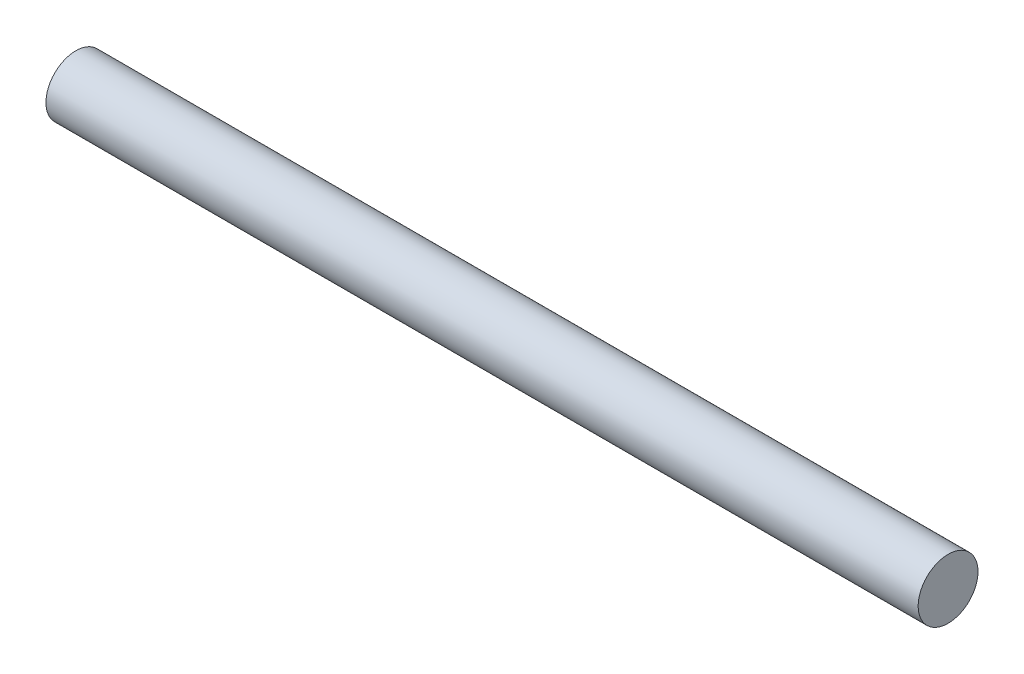
SolidWorks part; units mm, degrees
ref_plane "Front Plane" through (0, 0, 0) normal (0, 0, 1) x (1, 0, 0)
ref_plane "Top Plane" through (0, 0, 0) normal (0, 1, 0) x (1, 0, 0)
ref_plane "Right Plane" through (0, 0, 0) normal (1, 0, 0) x (0, 0, -1)
sketch "Sketch1" plane through (0, 0, 0) normal (1, 0, 0) x (0, 0, -1)
  circle A0 centre (0, 0) radius 2.4
  dimension "D1" = 4.8
extrude "Boss-Extrude1" add sketch "Sketch1" along normal mid plane 70 contours A0
